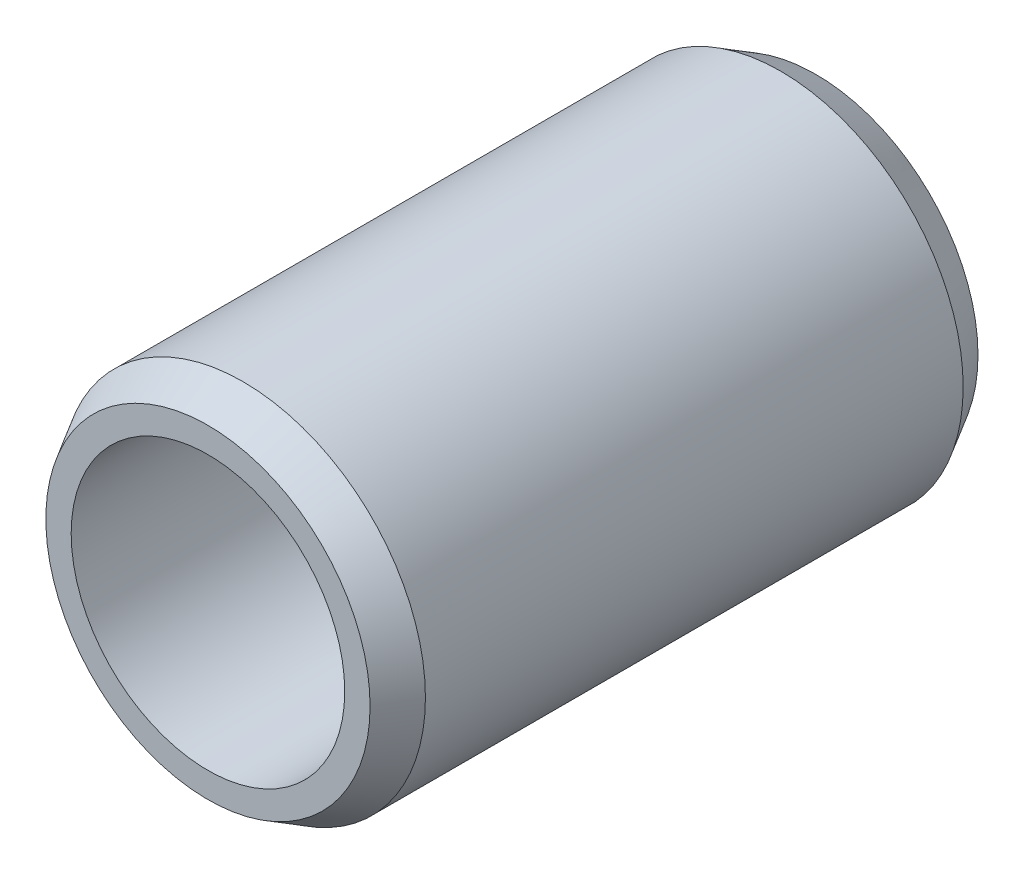
SolidWorks part; units mm, degrees
material "ABS"
ref_plane "Front Plane" through (0, 0, 0) normal (0, 0, 1) x (1, 0, 0)
ref_plane "Top Plane" through (0, 0, 0) normal (0, 1, 0) x (1, 0, 0)
ref_plane "Right Plane" through (0, 0, 0) normal (1, 0, 0) x (0, 0, -1)
sketch "Sketch1" plane through (0, 0, 0) normal (0, 0, 1) x (1, 0, 0)
  circle A0 centre (0, 0) radius 4.5
  circle A1 centre (0, 0) radius 3.375
  dimension "D1" = 6.75
  dimension "D2" = 9
extrude "Boss-Extrude1" add sketch "Sketch1" along normal blind 15
chamfer "Chamfer1" distance 0.5 angle 60 2 edges at (4.5, 0, 15) (4.5, 0, 0) first distance on face at (4.5, 0, 15) first distance on face at (4.5, 0, 0)
